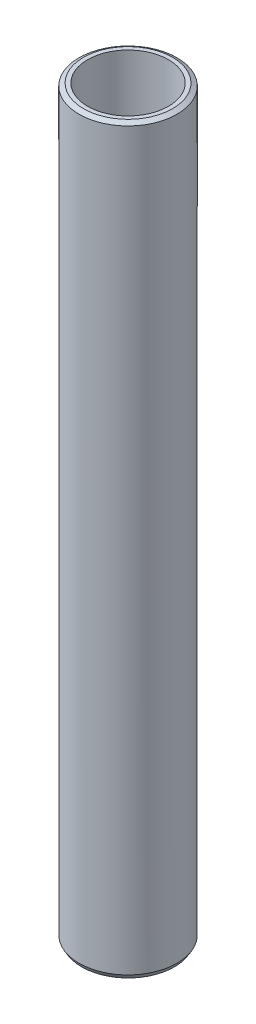
SolidWorks part; units mm, degrees
ref_plane "Front Plane" through (0, 0, 0) normal (0, 0, 1) x (1, 0, 0)
ref_plane "Top Plane" through (0, 0, 0) normal (0, 1, 0) x (1, 0, 0)
ref_plane "Right Plane" through (0, 0, 0) normal (1, 0, 0) x (0, 0, -1)
sketch "Sketch1" plane through (0, 0, 0) normal (0, 1, 0) x (1, 0, 0)
  circle A0 centre (0, 0) radius 25
  dimension "SHAFT_OD" = 50
extrude "Boss-Extrude1" add sketch "Sketch1" along normal blind 378.7212
sketch "Sketch2" plane through (0, 0, 0) normal (0, 1, 0) x (1, 0, 0)
  circle A0 centre (0, 0) radius 20.636
  dimension "BORE_D" = 41.2719
extrude "Cut-Extrude1" cut sketch "Sketch2" along normal through all
chamfer "Chamfer1" distance 1.3172 angle 60 2 edges at (0, 378.7212, 25) (0, 0, 25) first distance on face at (0, 378.7212, 25) first distance on face at (0, 0, 20.636)
